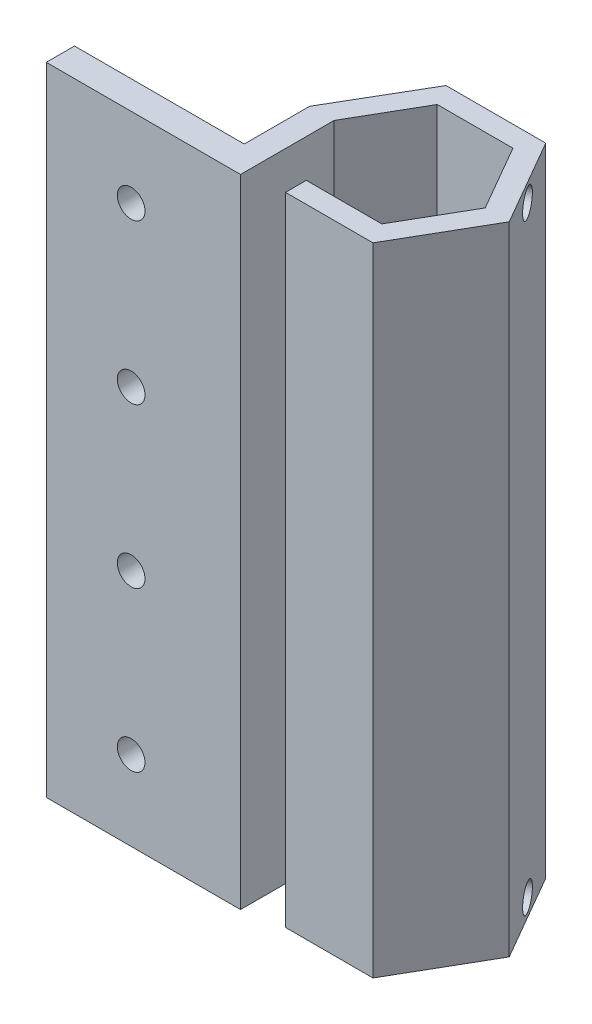
SolidWorks part; units mm, degrees
ref_plane "Front Plane" through (0, 0, 0) normal (0, 0, 1) x (1, 0, 0)
ref_plane "Top Plane" through (0, 0, 0) normal (0, 1, 0) x (1, 0, 0)
ref_plane "Right Plane" through (0, 0, 0) normal (1, 0, 0) x (0, 0, -1)
sketch "Sketch4" plane through (0, 0, 0) normal (0, 1, 0) x (1, 0, 0)
  line L1 (8.8623, 15.35) -> (-8.8623, 15.35) construction
  line L2 (-8.8623, 15.35) -> (-17.7247, 0) construction
  line L3 (-17.7247, 0) -> (-8.8623, -15.35) construction
  line L4 (-8.8623, -15.35) -> (8.8623, -15.35) construction
  line L5 (8.8623, -15.35) -> (17.7247, 0) construction
  line L6 (17.7247, 0) -> (8.8623, 15.35) construction
  line L30 (-17.8113, 0.05) -> (-17.8113, -22)
  line L33 (-23.5848, 0.05) -> (-23.5848, -15.35)
  line L36 (-8.8623, -20.35) -> (11.7491, -20.35)
  line L39 (-23.5848, -15.35) -> (-63.5848, -15.35)
  line L40 (-63.5848, -22) -> (-63.5848, -15.35)
  line L41 (-63.5848, -22) -> (-17.8113, -22)
  line L42 (-8.8623, -15.45) -> (8.9201, -15.45)
  line L43 (8.9201, -15.45) -> (17.8401, 0)
  line L44 (17.8401, 0) -> (8.9201, 15.45)
  line L45 (8.9201, 15.45) -> (-8.9201, 15.45)
  line L46 (-8.9201, 15.45) -> (-17.8113, 0.05)
  line L47 (11.7491, -20.35) -> (23.4982, 0)
  line L48 (23.4982, 0) -> (11.7491, 20.35)
  line L49 (11.7491, 20.35) -> (-11.7491, 20.35)
  line L50 (-11.7491, 20.35) -> (-23.5848, 0.05)
  line L51 (-11.7491, 20.35) -> (-22.0548, 2.5) construction
  line L52 (-8.8623, -20.35) -> (-8.8623, -15.45)
  circle A0 centre (0, 0) radius 15.35 construction
  point P24 (-8.8623, -20.35)
  point P27 (-17.7247, -22)
  dimension "D2" = 0.1
  dimension "D1" = 30.7
  dimension "D3" = 5
  dimension "D4" = 6.65
  dimension "D5" = 22.05
  dimension "D6" = 40
  dimension "D7" = 15.4
  dimension "D8" = 20.3
  dimension "D9" = 179.756
extrude "Boss-Extrude3" add sketch "Sketch4" against normal blind 150 contours L39 L40 L41 L30 L46 L45 L44 L43 L42 L52 L36 L47 L48 L49 L50 L33
sketch "Sketch5" plane through (0, 0, 15.35) normal (0, 0, -1) x (-1, 0, 0)
  line L2 (23.5848, -150) -> (63.5848, -150) construction
  line L3 (43.5848, -75) -> (63.5848, -75) construction
  line L4 (63.5848, -150) -> (63.5848, 0) construction
  line L8 (43.5848, -112.5) -> (63.5848, -112.5) construction
  line L9 (43.5848, -75) -> (43.5848, -112.5) construction
  line L13 (43.5848, -150) -> (43.5848, -112.5) construction
  line L14 (43.5848, -112.5) -> (43.5848, -150) construction
  line L17 (43.5848, -37.5) -> (63.5848, -37.5) construction
  line L18 (43.5848, -37.5) -> (43.5848, -75) construction
  line L19 (43.5848, 0) -> (43.5848, -37.5) construction
  line L20 (23.5848, 0) -> (63.5848, 0) construction
  circle A3 centre (43.5848, -131.25) radius 3.2639
  circle A4 centre (43.5848, -93.75) radius 3.2639
  circle A5 centre (43.5848, -56.25) radius 3.2639
  circle A6 centre (43.5848, -18.75) radius 3.2639
  dimension "D4" = 6.5278
extrude "Cut-Extrude1" cut sketch "Sketch5" against normal blind 10 contours A3 | A4 | A5 | A6
sketch "Sketch6" plane through (17.6236, 0, -10.175) normal (0.866, 0, -0.5) x (-0.5, 0, -0.866)
  line L0 (0, 0) -> (0, -150) construction
  line L2 (-11.7491, -150) -> (11.7491, -150) construction
  line L4 (0, 0) -> (0, -1) construction
  line L5 (0, -7.3) -> (0, -25.7) construction
  line L7 (0, -150) -> (0, -149) construction
  circle A2 centre (0, -4.15) radius 3.15
  circle A3 centre (0, -145.85) radius 3.15
  dimension "D1" = 1
  dimension "D2" = 6.3
  dimension "D4" = 6.3
  dimension "D3" = 1
  dimension "D5" = 18.4
extrude "Cut-Extrude3" cut sketch "Sketch6" against normal blind 10 contours A3 | A2
sketch "Sketch7" plane through (17.6236, 0, -10.175) normal (0.866, 0, -0.5) x (-0.5, 0, -0.866)
  line L0 (0, -7.3) -> (0, -25.7) construction
  line L1 (-11.7491, -25.7) -> (11.7491, -25.7)
  line L2 (-11.7491, -150) -> (-11.7491, 0) construction
  line L4 (11.7491, -25.7) -> (11.7491, -27.2994)
  line L5 (11.7491, -27.2994) -> (-11.7491, -27.2994)
  line L6 (-11.7491, -27.2994) -> (-11.7491, -25.7)
  line L7 (0, -142.7) -> (0, -124.3) construction
  line L8 (-11.7491, -124.3) -> (11.7491, -124.3)
  line L9 (11.7491, -124.3) -> (11.7491, -122.7)
  line L10 (11.7491, -122.7) -> (-11.7491, -122.7)
  line L11 (-11.7491, -122.7) -> (-11.7491, -124.3)
  line L12 (11.7491, -150) -> (11.7491, 0) construction
  line L13 (11.7491, -150) -> (11.7491, 0) construction
  circle A0 centre (0, -4.15) radius 3.15 construction
  circle A1 centre (0, -145.85) radius 3.15 construction
  dimension "D1" = 18.4
  dimension "D2" = 18.4
  dimension "D3" = 1.6
  dimension "D4" = 1.5994
extrude "Boss-Extrude4" add sketch "Sketch7" against normal blind 10
